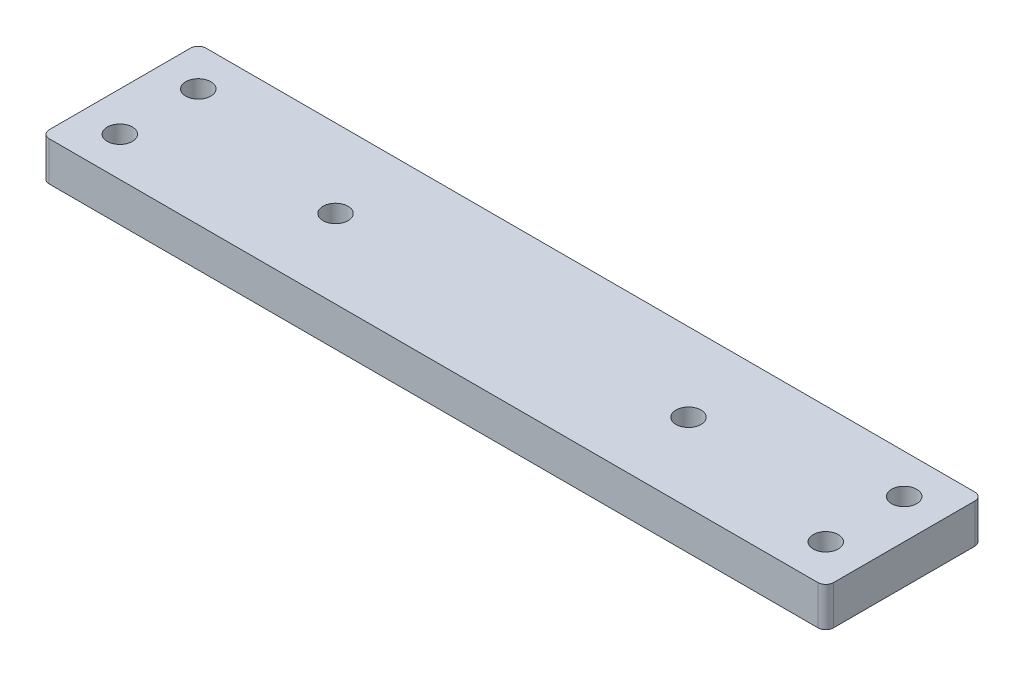
SolidWorks part; units mm, degrees
ref_plane "Plan de face" through (0, 0, 0) normal (0, 0, 1) x (1, 0, 0)
ref_plane "Plan de dessus" through (0, 0, 0) normal (0, 1, 0) x (1, 0, 0)
ref_plane "Plan de droite" through (0, 0, 0) normal (1, 0, 0) x (0, 0, -1)
ref_plane "Plan1" through (0, 5, 0) normal (0, 1, 0) x (1, 0, 0)
sketch "Esquisse1" plane through (0, 5, 0) normal (0, 1, 0) x (1, 0, 0)
  line L0 (50, -20) -> (50, 0)
  line L1 (50, 0) -> (-50, 0)
  line L2 (-50, 0) -> (-50, -20)
  line L3 (-50, -20) -> (50, -20)
extrude "Boss.-Extru.1" add sketch "Esquisse1" against normal blind 5
hole_wizard "Diamètre du perçage Ø3.2 (3.2)1" positions "Esquisse3" profile "Esquisse2" hole size "Ø3.2" standard "Ansi Metric" end condition through all
sketch "Esquisse3" plane through (0, 5, 0) normal (0, 1, 0) x (1, 0, 0)
  point P0 (22.5, -10)
  point P1 (-22.5, -10)
sketch "Esquisse2" plane through (22.5, 5, 10) normal (1, 0, 0) x (0, 0, 1)
  line L0 (0, 0) -> (0, 5)
  line L1 (0, 5) -> (1.6, 5)
  line L2 (1.6, 5) -> (1.6, 0)
  line L5 (1.6, 0) -> (0, 0)
  line L11 (0, -6.35) -> (0, 107.95) construction
  dimension "Diamètre du perçage jusqu'au prochain" = 3.2
  dimension "Profondeur du perçage jusqu'au prochain" = 5
hole_wizard "Diamètre du perçage Ø3.2 (3.2)2" positions "Esquisse5" profile "Esquisse4" hole size "Ø3.2" standard "Ansi Metric"
sketch "Esquisse5" plane through (0, 0, 0) normal (0, -1, 0) x (-1, 0, 0)
  line L0 (50, -20) -> (-50, -20) construction
  line L1 (-50, -20) -> (-50, 0) construction
  point P0 (45, -15)
  point P1 (45, -5)
  point P2 (-45, -5)
  point P3 (-45, -15)
  dimension "D1" = 5
  dimension "D2" = 5
  dimension "D3" = 10
sketch "Esquisse4" plane through (-45, 0, 15) normal (1, 0, 0) x (0, 0, -1)
  line L0 (0, 0) -> (0, 5)
  line L1 (0, 5) -> (1.6, 5)
  line L2 (1.6, 5) -> (1.6, 0)
  line L5 (1.6, 0) -> (0, 0)
  line L11 (0, -6.35) -> (0, 107.95) construction
  dimension "Diamètre du perçage jusqu'au prochain" = 3.2
  dimension "Profondeur du perçage jusqu'au prochain" = 5
fillet "Congé1" radius 1 4 edges at (50, 2.5, 0) (-50, 2.5, 20) (50, 2.5, 20) (-50, 2.5, 0) tangent propagation no
